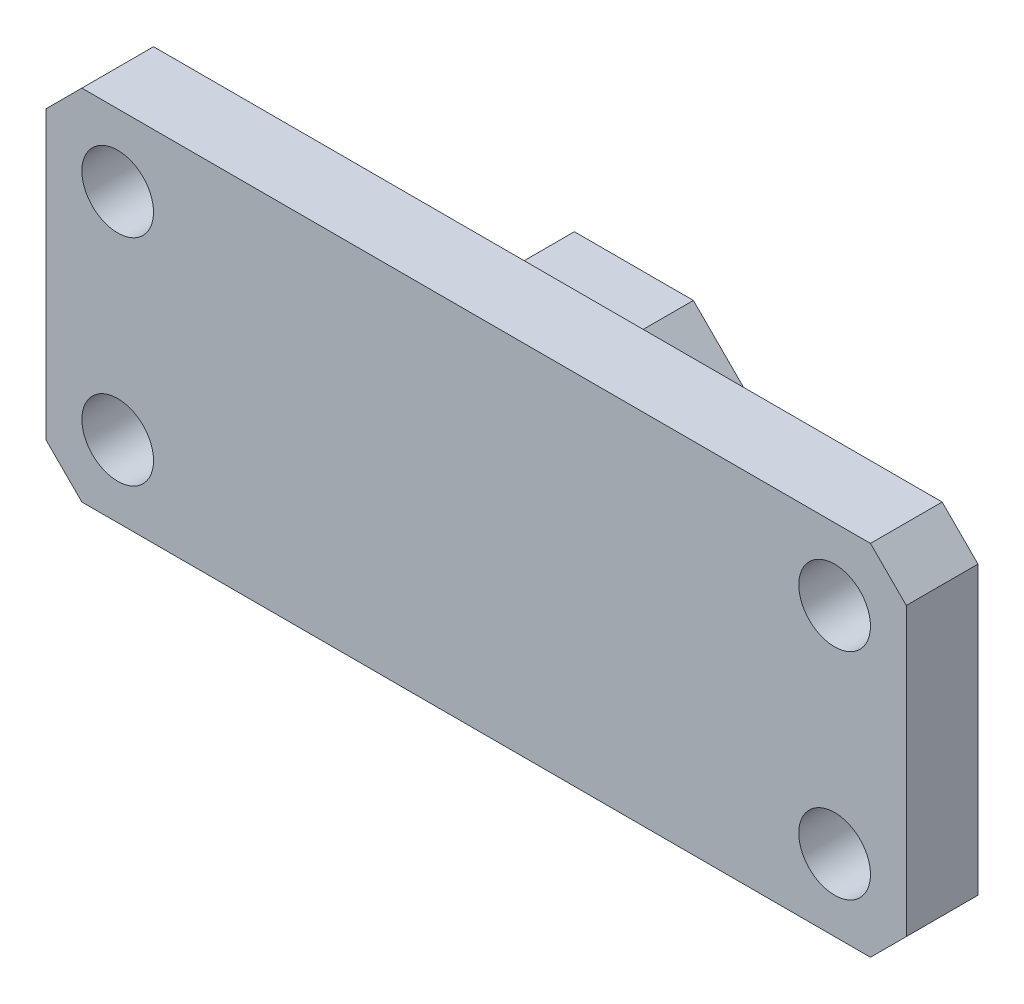
SolidWorks part; units mm, degrees
ref_plane "Спереди" through (0, 0, 0) normal (0, 0, 1) x (1, 0, 0)
ref_plane "Сверху" through (0, 0, 0) normal (0, 1, 0) x (1, 0, 0)
ref_plane "Справа" through (0, 0, 0) normal (1, 0, 0) x (0, 0, -1)
sketch "Эскиз доски" plane through (0, 0, 0) normal (0, 0, 1) x (1, 0, 0)
  line L0 (-60, 0) -> (60, 0) construction
  line L1 (-60, 25) -> (60, 25)
  line L2 (-60, 25) -> (-60, -25)
  line L3 (-60, -25) -> (60, -25)
  line L4 (60, 25) -> (60, -25)
  line L5 (-60, 25) -> (60, -25) construction
  line L6 (-60, -25) -> (60, 25) construction
  line L7 (0, 25) -> (0, -25) construction
  circle A0 centre (50, 15) radius 5
  circle A1 centre (-50, 15) radius 5
  circle A2 centre (-50, -15) radius 5
  circle A3 centre (50, -15) radius 5
  point P0 (0, 0)
  point P9 (51.0903, 10.1203)
  point P12 (0, 0)
  point P13 (0, 0)
  point P14 (0, 0)
  point P21 (49.5033, 8.1136)
  point P22 (0, 0)
  point P24 (44.6762, 11.7083)
  point P25 (44.5735, 13.3)
  point P26 (44.5735, 13.3)
  point P27 (47.5016, 12.631)
  point P28 (51.1046, 13.1765)
  point P29 (47.81, 12.7949)
  point P30 (49.1063, 13.2195)
  point P31 (-48.9097, 15)
  point P32 (0, 0)
  dimension "D4" = 10
  dimension "D1" = 50
  dimension "D2" = 10
  dimension "D5" = 120
  dimension "D6" = 10
extrude "Доска" add sketch "Эскиз доски" along normal blind 10 contours L1 L4 L3 L2
extrude "Отверстия в доске" cut sketch "Эскиз1<5>" against normal blind 10 from offset 10 contours A0 | A1 | A2 | A3
sketch "Эскиз1<5>" plane through (0, 0, 0) normal (0, 0, 1) x (1, 0, 0) same geometry as "Эскиз доски"
chamfer "Края доски" distance 5 angle 45 4 edges at (-60, 25, 5) (-60, -25, 5) (60, -25, 5) (60, 25, 5)
sketch "Эскиз2" plane through (0, 0, 0) normal (0, 0, -1) x (-1, 0, 0)
  line L0 (60, 0) -> (-60, 0) construction
  line L1 (0, 25) -> (0, -25) construction
  line L2 (-8.3, 20) -> (8.3, 20)
  line L5 (8.3, 20) -> (20, 8.3)
  line L6 (20, 8.3) -> (35, 8.3)
  line L7 (35, 8.3) -> (35, -8.3)
  line L8 (0, 25) -> (0, -25) construction
  line L9 (-8.3, 20) -> (-20, 8.3)
  line L10 (-20, 8.3) -> (-35, 8.3)
  line L11 (-35, 8.3) -> (-35, -8.3)
  line L12 (-20, -8.3) -> (-35, -8.3)
  line L13 (-8.3, -20) -> (-20, -8.3)
  line L14 (-8.3, -20) -> (8.3, -20)
  line L15 (8.3, -20) -> (20, -8.3)
  line L16 (20, -8.3) -> (35, -8.3)
  circle A0 centre (0, 0) radius 10
  point P12 (0, 0)
  point P14 (0, 0)
  point P18 (0, 0)
  point P20 (0, 20)
  point P24 (-35, 0)
  point P29 (35, 0)
  dimension "D6" = 20
  dimension "D1" = 8.3
  dimension "D2" = 15
  dimension "D3" = 11.7
  dimension "D4" = 8.3
  dimension "D5" = 11.7
extrude "Бобышка-Вытянуть2" add sketch "Эскиз2" along normal blind 22 from surface contours L9 L10 L11 L12 L13 L14 L15 L16 L7 L6 L5 L2 starting at face at (-55, 15, 10)
